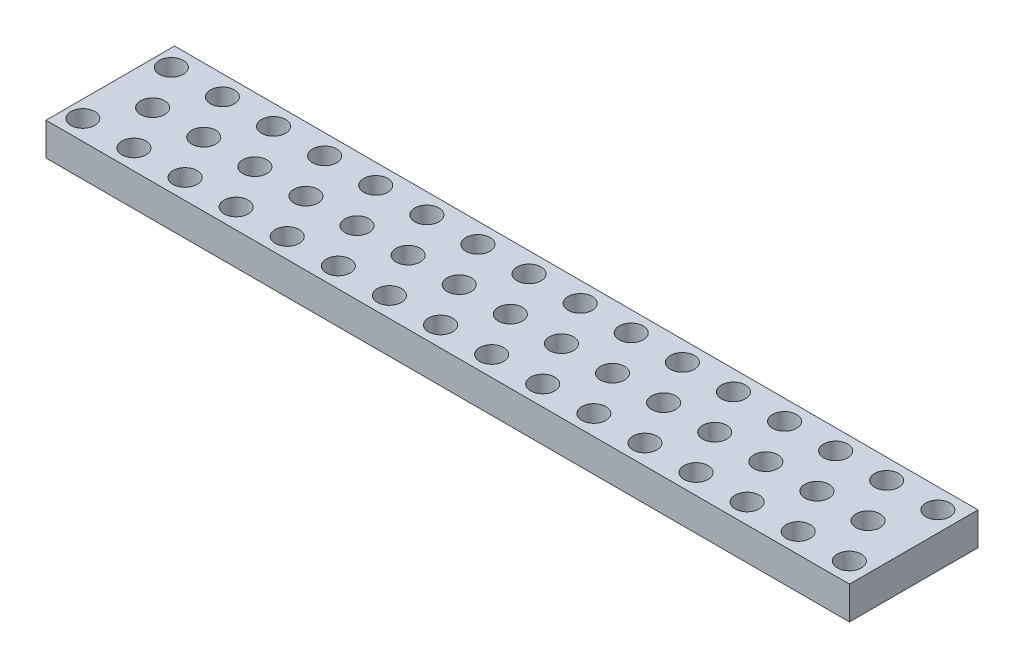
SolidWorks part; units mm, degrees
ref_plane "Front Plane" through (0, 0, 0) normal (0, 0, 1) x (1, 0, 0)
ref_plane "Top Plane" through (0, 0, 0) normal (0, 1, 0) x (1, 0, 0)
ref_plane "Right Plane" through (0, 0, 0) normal (1, 0, 0) x (0, 0, -1)
sketch "Sketch1" plane through (0, 0, 0) normal (0, 1, 0) x (1, 0, 0)
  line L0 (0, 0) -> (20.193, 0) construction
  line L1 (20.193, 0) -> (20.193, 34.9758) construction
  line L2 (20.193, 34.9758) -> (20.193, 44.5008) construction
  line L3 (36.068, -50.7492) -> (-598.932, -50.7492)
  line L4 (36.068, -50.7492) -> (36.068, 50.8508)
  line L5 (36.068, 50.8508) -> (-598.932, 50.8508)
  line L6 (-598.932, -50.7492) -> (-598.932, 50.8508)
  line L7 (20.193, 34.9758) -> (29.718, 34.9758) construction
  circle A0 centre (0, 0) radius 9.525
  circle A1 centre (20.193, 34.9758) radius 9.525
  circle A2 centre (20.193, -34.9758) radius 9.525
  dimension "D1" = 19.05
  dimension "D4" = 19.05
  dimension "D2" = 20.193
  dimension "D3" = 34.9758
  dimension "D5" = 6.35
  dimension "D6" = 6.35
  dimension "D7" = 101.6
  dimension "D8" = 635
extrude "Boss-Extrude1" add sketch "Sketch1" against normal blind 25.908 contours L5 L6 L3 L4
extrude "Cut-Extrude1" cut sketch "Sketch1<3>" against normal through all both and the other way through all contours A0 | A1 | A2 region at (0, 0, 0) region at (20.193, 0, -34.9758) region at (20.193, 0, 34.9758)
sketch "Sketch1<3>" plane through (0, 0, 0) normal (0, 1, 0) x (1, 0, 0) same geometry as "Sketch1"
pattern_linear "LPattern1" count 15 spacing 40.386 along (-1, 0, 0) of "Cut-Extrude1"
sketch "Sketch2" plane through (0, 0, 0) normal (0, 1, 0) x (1, 0, 0)
  line L0 (-545.211, 34.9758) -> (-585.597, 34.9758) construction
  line L1 (-585.597, 34.9758) -> (-595.122, 34.9758) construction
  line L3 (-565.404, 0) -> (-524.844, 0) construction
  circle A0 centre (-585.597, 34.9758) radius 9.525
  circle A1 centre (-585.597, -34.9758) radius 9.525
  dimension "D2" = 19.05
  dimension "D1" = 40.386
extrude "Cut-Extrude2" cut sketch "Sketch2" against normal through all both contours A0 | A1
sketch "Sketch3" plane through (0, 0, 0) normal (0, 1, 0) x (1, 0, 0)
  line L1 (20.193, 34.9758) -> (36.068, 34.9758) construction
  line L3 (36.068, -50.7492) -> (36.068, 50.8508) construction
ref_plane "Plane1" through (20.066, 0, 0) normal (1, 0, 0) x (0, 0, -1)
